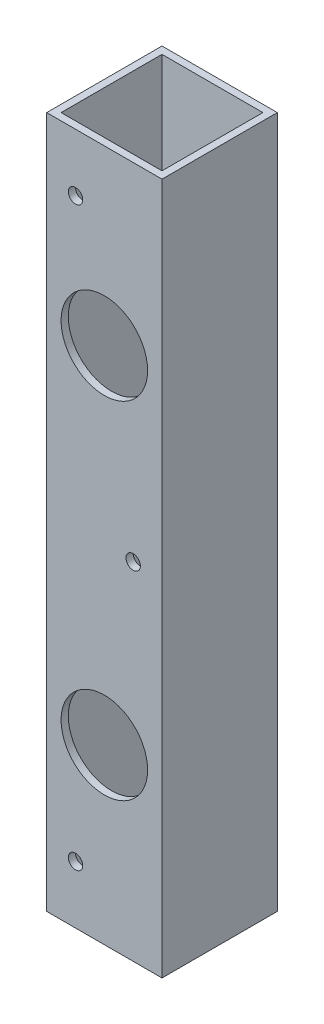
SolidWorks part; units mm, degrees
ref_plane "Front Plane" through (0, 0, 0) normal (0, 0, 1) x (1, 0, 0)
ref_plane "Top Plane" through (0, 0, 0) normal (0, 1, 0) x (1, 0, 0)
ref_plane "Right Plane" through (0, 0, 0) normal (1, 0, 0) x (0, 0, -1)
sketch "Sketch1" plane through (0, 0, 0) normal (0, 1, 0) x (1, 0, 0)
  line L1 (12.7, -12.7) -> (-12.7, -12.7)
  line L2 (12.7, -12.7) -> (12.7, 12.7)
  line L3 (12.7, 12.7) -> (-12.7, 12.7)
  line L4 (-12.7, -12.7) -> (-12.7, 12.7)
  line L5 (12.7, -12.7) -> (-12.7, 12.7) construction
  line L6 (12.7, 12.7) -> (-12.7, -12.7) construction
  point P0 (0, 0)
  dimension "D1" = 25.4
extrude "Extrude-Thin1" add sketch "Sketch1" along normal blind 152.4 thin thin type one direction reverse wall 1.5875
sketch "Sketch2" plane through (0, 0, 12.7) normal (0, 0, 1) x (1, 0, 0)
  line L0 (-12.7, 0) -> (12.7, 0) construction
  line L1 (-6.35, 139.7) -> (6.35, 76.2) construction
  line L2 (6.35, 76.2) -> (-6.35, 12.7) construction
  line L6 (-12.7, 152.4) -> (-12.7, 0) construction
  line L7 (-12.7, 152.4) -> (12.7, 152.4) construction
  line L8 (12.7, 152.4) -> (12.7, 0) construction
  circle A0 centre (0, 114.3) radius 9.525
  circle A1 centre (0, 38.1) radius 9.525
  circle A7 centre (-6.35, 139.7) radius 1.5875
  circle A8 centre (6.35, 76.2) radius 1.5875
  circle A9 centre (-6.35, 12.7) radius 1.5875
  dimension "D1" = 19.05
  dimension "D2" = 38.1
  dimension "D3" = 114.3
  dimension "D4" = 3.175
  dimension "D5" = 6.35
  dimension "D6" = 12.7
  dimension "D7" = 6.35
  dimension "D8" = 12.7
extrude "Cut-Extrude1" cut sketch "Sketch2" against normal up to next
sketch "Sketch4" plane through (0, 0, -11.1125) normal (0, 0, 1) x (1, 0, 0)
  circle A0 centre (0, 114.3) radius 3.3782
  circle A1 centre (0, 38.1) radius 3.3782
  dimension "D1" = 6.7564
extrude "Cut-Extrude2" cut sketch "Sketch4" against normal through all
